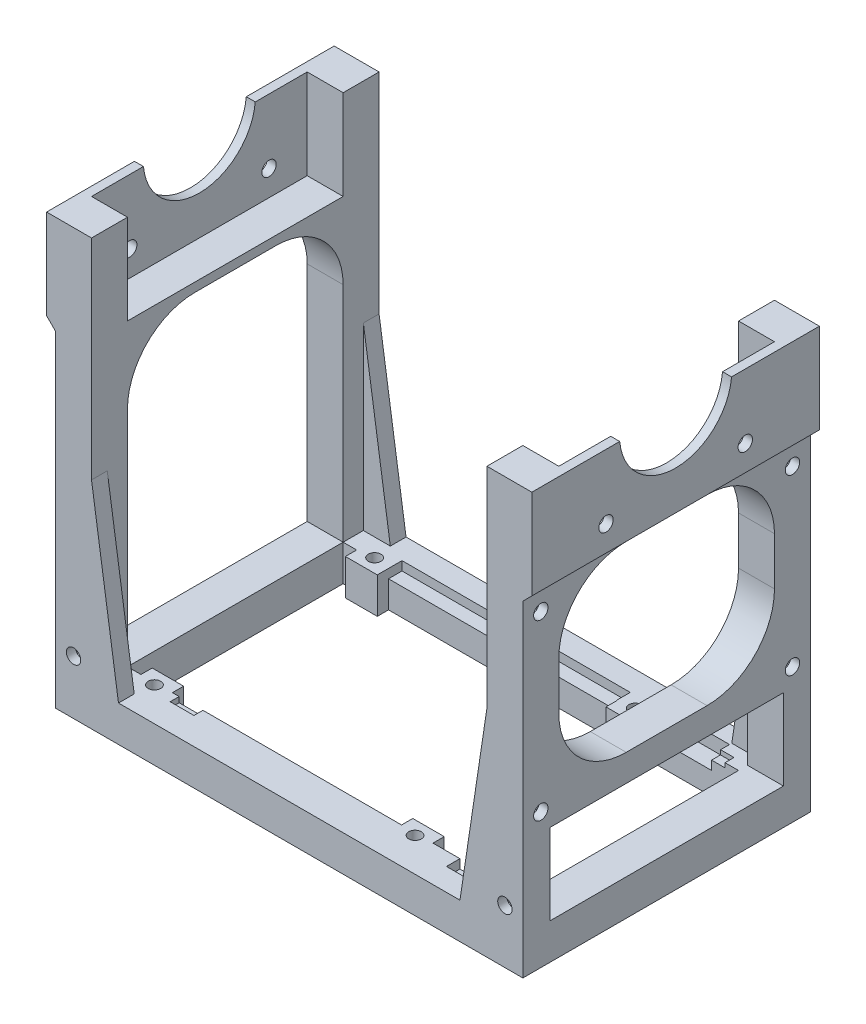
SolidWorks part; units mm, degrees
ref_plane "Płaszczyzna przednia" through (0, 0, 0) normal (0, 0, 1) x (1, 0, 0)
ref_plane "Płaszczyzna górna" through (0, 0, 0) normal (0, 1, 0) x (1, 0, 0)
ref_plane "Płaszczyzna prawa" through (0, 0, 0) normal (1, 0, 0) x (0, 0, -1)
sketch "Szkic1" plane through (0, 0, 0) normal (0, 1, 0) x (1, 0, 0)
  line L1 (0, 0) -> (108, 0)
  line L2 (0, 0) -> (0, 64)
  line L3 (0, 64) -> (108, 64)
  line L4 (108, 0) -> (108, 64)
  line L5 (0, 0) -> (8, 0)
  line L6 (0, 0) -> (0, 8)
  line L7 (0, 8) -> (8, 8)
  line L8 (8, 0) -> (8, 8)
  line L9 (108, 64) -> (100, 64)
  line L10 (108, 64) -> (108, 56)
  line L11 (108, 56) -> (100, 56)
  line L12 (100, 64) -> (100, 56)
  line L13 (8, 8) -> (100, 8)
  line L14 (8, 8) -> (8, 56)
  line L15 (8, 56) -> (100, 56)
  line L16 (100, 8) -> (100, 56)
  line L17 (8, 56) -> (0, 56)
  line L18 (8, 56) -> (8, 64)
  line L19 (8, 64) -> (0, 64)
  line L20 (0, 56) -> (0, 64)
  line L21 (100, 8) -> (108, 8)
  line L22 (100, 8) -> (100, 0)
  line L23 (100, 0) -> (108, 0)
  line L24 (108, 8) -> (108, 0)
extrude "Dodanie-wyciągnięcie1" add sketch "Szkic1" along normal blind 8 contours L14 L17 L2 L7 | L1 L8 L7 L2 | L17 L18 L3 L2 | L18 L15 L12 L3 | L3 L12 L11 L4 | L16 L21 L4 L11 | L21 L22 L1 L4 | L22 L13 L8 L1 region at (4, 0, -4) region at (54, 0, -4) region at (4, 0, -32) region at (104, 0, -4) region at (4, 0, -60) region at (104, 0, -32) region at (54, 0, -60) region at (104, 0, -60)
sketch "Szkic2" plane through (0, 8, 0) normal (0, 1, 0) x (1, 0, 0)
  line L1 (0, 64) -> (8, 64)
  line L2 (0, 64) -> (0, 56)
  line L3 (0, 56) -> (8, 56)
  line L4 (8, 64) -> (8, 56)
  line L5 (8, 8) -> (0, 8)
  line L6 (8, 8) -> (8, 0)
  line L7 (8, 0) -> (0, 0)
  line L8 (0, 8) -> (0, 0)
  line L9 (100, 8) -> (108, 8)
  line L10 (100, 8) -> (100, 0)
  line L11 (100, 0) -> (108, 0)
  line L12 (108, 8) -> (108, 0)
  line L13 (100, 56) -> (108, 56)
  line L14 (100, 56) -> (100, 64)
  line L15 (100, 64) -> (108, 64)
  line L16 (108, 56) -> (108, 64)
extrude "Dodanie-wyciągnięcie3" add sketch "Szkic2" along normal blind 64
sketch "Szkic5" plane through (108, 0, 0) normal (1, 0, 0) x (0, 0, -1)
  line L0 (8, 72) -> (8, 8) construction
  line L1 (6, 8) -> (8, 8)
  line L2 (6, 8) -> (6, 26)
  line L3 (6, 26) -> (8, 26)
  line L4 (8, 8) -> (8, 26)
  line L5 (56, 72) -> (56, 8) construction
  line L6 (58, 8) -> (56, 8)
  line L7 (58, 8) -> (58, 26)
  line L8 (58, 26) -> (56, 26)
  line L9 (56, 8) -> (56, 26)
extrude "Wytnij-wyciągnięcie2" cut sketch "Szkic5" against normal blind 8
sketch "Szkic6" plane through (0, 0, -8) normal (0, 0, -1) x (-1, 0, 0)
  line L0 (-100, 72) -> (-100, 26) construction
  line L1 (-108, 26) -> (-100, 26)
  line L2 (-108, 26) -> (-108, 32)
  line L3 (-108, 32) -> (-100, 32)
  line L4 (-100, 26) -> (-100, 32)
extrude "Dodanie-wyciągnięcie5" add sketch "Szkic6" along normal blind 48
sketch "Szkic7" plane through (0, 8, 0) normal (0, 1, 0) x (1, 0, 0)
  line L0 (8, 56) -> (100, 56) construction
  line L1 (22.1, 56) -> (72.9, 56)
  line L2 (22.1, 56) -> (22.1, 59)
  line L3 (22.1, 59) -> (72.9, 59)
  line L4 (72.9, 56) -> (72.9, 59)
  line L5 (22.1, 54.36) -> (22.1, 56.1) construction
  line L6 (23.37, 57.77) -> (22.1, 57.77) construction
  line L7 (71.63, 57.77) -> (72.9, 57.77) construction
extrude "Wytnij-wyciągnięcie3" cut sketch "Szkic7" against normal blind 2
sketch "Szkic12" plane through (0, 8, 0) normal (0, 1, 0) x (1, 0, 0)
  line L0 (18.5, 57.85) -> (18.5, 55.15) construction
  line L1 (18.5, 56.5) -> (18.5, 53.5) construction
  line L2 (18.5, 56.5) -> (22.1, 56.5)
  line L3 (22.1, 59) -> (22.1, 56) construction
  line L4 (22.1, 56.5) -> (22.1, 53.5)
  line L5 (22.1, 53.5) -> (18.5, 53.5)
  line L6 (18.5, 53.5) -> (15, 53.5)
  line L7 (15, 57) -> (15, 7) construction
  line L8 (15, 53.5) -> (15, 56.5)
  line L9 (15, 56.5) -> (18.5, 56.5)
  circle A0 centre (18.5, 56.5) radius 1.35 construction
  circle A1 centre (18.5, 56.5) radius 1.75
  circle A2 centre (18.5, 56.5) radius 3 construction
  line M23 (8, 56) -> (22.1, 56)
extrude "Dodanie-wyciągnięcie7" add sketch "Szkic12" against normal blind 8 contours A1 L8 L6 L5 L4 M23 | A1 M23 region at (18.5605, 8, -54.5963) region at (18.5, 8, -55.4806)
sketch "Szkic14" plane through (0, 8, 0) normal (0, 1, 0) x (1, 0, 0)
  line L0 (18.5, 8.85) -> (18.5, 6.15) construction
  line L1 (18.5, 7.5) -> (15, 7.5)
  line L2 (15, 57) -> (15, 7) construction
  line L4 (18.5, 10.5) -> (22, 10.5)
  line L5 (22, 10.5) -> (22, 7.5)
  line L6 (22, 7.5) -> (18.5, 7.5)
  line L7 (15, 7.5) -> (15, 10.5)
  line L8 (15, 10.5) -> (18.5, 10.5)
  circle A0 centre (18.5, 7.5) radius 1.35 construction
  circle A1 centre (18.5, 7.5) radius 3 construction
extrude "Dodanie-wyciągnięcie8" add sketch "Szkic14" against normal blind 8
sketch "Szkic15" plane through (0, 8, 0) normal (0, 1, 0) x (1, 0, 0)
  line L0 (76.5, 56.5) -> (76.5, 53.5) construction
  line L1 (76.5, 53.5) -> (73, 53.5)
  line L2 (73, 53.5) -> (73, 56.5)
  line L3 (73, 56.5) -> (76.5, 56.5)
  line L4 (76.5, 56.5) -> (80, 56.5)
  line L5 (80, 56.5) -> (80, 53.5)
  line L6 (80, 53.5) -> (76.5, 53.5)
  circle A0 centre (76.5, 56.5) radius 3 construction
extrude "Dodanie-wyciągnięcie9" add sketch "Szkic15" against normal blind 8
sketch "Szkic16" plane through (0, 8, 0) normal (0, 1, 0) x (1, 0, 0)
  line L0 (76.5, 7.5) -> (76.5, 10.5) construction
  line L1 (76.5, 7.5) -> (80, 7.5)
  line L2 (80, 7.5) -> (80, 10.5)
  line L3 (80, 10.5) -> (76.5, 10.5)
  line L4 (76.5, 10.5) -> (73, 10.5)
  line L5 (73, 10.5) -> (73, 7.5)
  line L6 (73, 7.5) -> (76.5, 7.5)
  circle A0 centre (76.5, 7.5) radius 3 construction
extrude "Dodanie-wyciągnięcie10" add sketch "Szkic16" against normal blind 8
sketch "Szkic17" plane through (0, 8, 0) normal (0, 1, 0) x (1, 0, 0)
  line L0 (18.5, 7.5) -> (21.1, 4.9) construction
  line L1 (73.9, 4.9) -> (79.1, 4.9)
  line L2 (79.1, 4.9) -> (79.1, 10.1)
  line L3 (79.1, 10.1) -> (73.9, 10.1)
  line L4 (73.9, 10.1) -> (73.9, 4.9)
  line L5 (15.9, 59.1) -> (15.9, 53.9)
  line L6 (15.9, 53.9) -> (21.1, 53.9)
  line L7 (21.1, 10.1) -> (15.9, 10.1)
  line L8 (21.1, 10.1) -> (21.1, 4.9)
  line L9 (21.1, 4.9) -> (15.9, 4.9)
  line L10 (15.9, 10.1) -> (15.9, 4.9)
  line L11 (21.1, 53.9) -> (21.1, 59.1)
  line L12 (21.1, 59.1) -> (15.9, 59.1)
  line L13 (79.1, 59.1) -> (73.9, 59.1)
  line L14 (73.9, 59.1) -> (73.9, 53.9)
  line L15 (73.9, 53.9) -> (79.1, 53.9)
  line L16 (79.1, 53.9) -> (79.1, 59.1)
  line L17 (18.5, 7.5) -> (21.1, 10.1) construction
  line L18 (15.9, 4.9) -> (18.5, 7.5) construction
  line L19 (18.5, 7.5) -> (15.9, 10.1) construction
  circle A3 centre (76.5, 7.5) radius 2.6 construction
  circle A4 centre (18.5, 56.5) radius 2.6 construction
  circle A5 centre (76.5, 56.5) radius 2.6 construction
extrude "Wytnij-wyciągnięcie8" cut sketch "Szkic17" against normal blind 4
sketch "Szkic18" plane through (0, 8, 0) normal (0, 1, 0) x (1, 0, 0)
  line L0 (15.9, 53.9) -> (21.1, 59.1) construction
  line L1 (73.9, 53.9) -> (79.1, 59.1) construction
  line L2 (15.9, 10.1) -> (21.1, 4.9) construction
  line L3 (73.9, 10.1) -> (79.1, 4.9) construction
  circle A0 centre (18.5, 56.5) radius 1.4
  circle A1 centre (18.5, 7.5) radius 1.4
  circle A2 centre (76.5, 7.5) radius 1.4
  circle A3 centre (76.5, 56.5) radius 1.4
extrude "Wytnij-wyciągnięcie9" cut sketch "Szkic18" against normal blind 4.5
sketch "Szkic19" plane through (0, 8, 0) normal (0, 1, 0) x (1, 0, 0)
  line L0 (15.9, 53.9) -> (21.1, 59.1) construction
  line L1 (15.9, 53.9) -> (21.1, 53.9)
  line L2 (15.9, 53.9) -> (15.9, 59.1)
  line L3 (15.9, 59.1) -> (21.1, 59.1)
  line L4 (21.1, 53.9) -> (21.1, 59.1)
  line L5 (15.9, 10.1) -> (21.1, 10.1)
  line L6 (15.9, 10.1) -> (15.9, 4.9)
  line L7 (15.9, 4.9) -> (21.1, 4.9)
  line L8 (21.1, 10.1) -> (21.1, 4.9)
  line L9 (73.9, 4.9) -> (79.1, 4.9)
  line L10 (73.9, 4.9) -> (73.9, 10.1)
  line L11 (73.9, 10.1) -> (79.1, 10.1)
  line L12 (79.1, 4.9) -> (79.1, 10.1)
  line L13 (73.9, 53.9) -> (79.1, 53.9)
  line L14 (73.9, 53.9) -> (73.9, 59.1)
  line L15 (73.9, 59.1) -> (79.1, 59.1)
  line L16 (79.1, 53.9) -> (79.1, 59.1)
  line L17 (73.9, 59.1) -> (79.1, 53.9) construction
  line L18 (79.1, 10.1) -> (73.9, 4.9) construction
  line L19 (21.1, 4.9) -> (15.9, 10.1) construction
  circle A0 centre (18.5, 56.5) radius 1.4
  circle A1 centre (76.5, 56.5) radius 1.4
  circle A2 centre (18.5, 7.5) radius 1.4
  circle A3 centre (76.5, 7.5) radius 1.4
extrude "Dodanie-wyciągnięcie11" add sketch "Szkic19" against normal blind 2.3
sketch "Szkic21" plane through (8, 0, 0) normal (1, 0, 0) x (0, 0, -1)
  line L1 (56, 8) -> (8, 8)
  line L2 (56, 8) -> (56, 0)
  line L3 (56, 0) -> (8, 0)
  line L4 (8, 8) -> (8, 0)
  line L5 (56, 8) -> (64, 8)
  line L6 (56, 8) -> (56, 72)
  line L7 (56, 72) -> (64, 72)
  line L8 (64, 8) -> (64, 72)
  line L9 (0, 72) -> (8, 72)
  line L10 (0, 72) -> (0, 8)
  line L11 (0, 8) -> (8, 8)
  line L12 (8, 72) -> (8, 8)
  line M9 (56, 8) -> (64, 8)
  line M10 (64, 8) -> (64, 72)
  line M11 (64, 72) -> (56, 72)
  line M12 (56, 72) -> (56, 8)
extrude "Dodanie-wyciągnięcie12" add sketch "Szkic21" along normal blind 4 contours M12 M9 M10 M11 | L12 L9 L10 L11 | L2 L1 L4 L3 region at (8, 40, -4) region at (8, 40, -60)
sketch "Szkic22" plane through (0, 0, 0) normal (0, -1, 0) x (1, 0, 0)
  line L0 (0, -64) -> (108, -64) construction
  line L1 (0, 0) -> (4, 0)
  line L2 (0, 0) -> (0, -64)
  line L3 (0, -64) -> (4, -64)
  line L4 (4, 0) -> (4, -64)
extrude "Wytnij-wyciągnięcie11" cut sketch "Szkic22" against normal blind 84 contours L2 L1 L4 L3
ref_plane "Płaszczyzna1" through (12, 8, -56) normal (1, 0, 0) x (0, 0, -1)
sketch "Szkic24" plane through (0, 72, 0) normal (0, 1, 0) x (1, 0, 0)
  line L1 (4, 64) -> (12, 64)
  line L2 (4, 64) -> (4, 56)
  line L3 (4, 56) -> (12, 56)
  line L4 (12, 64) -> (12, 56)
  line L5 (4, 8) -> (12, 8)
  line L6 (4, 8) -> (4, 0)
  line L7 (4, 0) -> (12, 0)
  line L8 (12, 8) -> (12, 0)
  line L9 (100, 8) -> (108, 8)
  line L10 (100, 8) -> (100, 0)
  line L11 (100, 0) -> (108, 0)
  line L12 (108, 8) -> (108, 0)
  line L13 (100, 64) -> (108, 64)
  line L14 (100, 64) -> (100, 56)
  line L15 (100, 56) -> (108, 56)
  line L16 (108, 64) -> (108, 56)
extrude "Dodanie-wyciągnięcie13" add sketch "Szkic24" along normal blind 2.64 contours L8 L5 L6 L7 | L12 L9 L10 L11 | L16 L13 L14 L15 | L2 L1 L4 L3 region at (8, 72, -4) region at (104, 72, -4) region at (104, 72, -60)
sketch "Szkic25" plane through (0, 0, -8) normal (0, 0, -1) x (-1, 0, 0)
  line L0 (-100, 74.64) -> (-100, 32) construction
  line L1 (-108, 74.64) -> (-100, 74.64)
  line L2 (-108, 74.64) -> (-108, 72.64)
  line L3 (-108, 72.64) -> (-100, 72.64)
  line L4 (-100, 74.64) -> (-100, 72.64)
  line L5 (-4, 74.64) -> (-4, 8) construction
  line L6 (-12, 74.64) -> (-4, 74.64)
  line L7 (-12, 74.64) -> (-12, 72.64)
  line L8 (-12, 72.64) -> (-4, 72.64)
  line L9 (-4, 74.64) -> (-4, 72.64)
extrude "Dodanie-wyciągnięcie14" add sketch "Szkic25" along normal blind 48
sketch "Szkic26" plane through (0, 74.64, 0) normal (0, 1, 0) x (1, 0, 0)
  line L1 (4, 64) -> (12, 64)
  line L2 (4, 64) -> (4, 56)
  line L3 (4, 56) -> (12, 56)
  line L4 (12, 64) -> (12, 56)
  line L5 (4, 0) -> (12, 0)
  line L6 (4, 0) -> (4, 8)
  line L7 (4, 8) -> (12, 8)
  line L8 (12, 0) -> (12, 8)
  line L9 (108, 0) -> (100, 0)
  line L10 (108, 0) -> (108, 8)
  line L11 (108, 8) -> (100, 8)
  line L12 (100, 0) -> (100, 8)
  line L13 (108, 64) -> (100, 64)
  line L14 (108, 64) -> (108, 56)
  line L15 (108, 56) -> (100, 56)
  line L16 (100, 64) -> (100, 56)
extrude "Dodanie-wyciągnięcie15" add sketch "Szkic26" along normal blind 20
sketch "Szkic27" plane through (4, 0, 0) normal (-1, 0, 0) x (0, 0, 1)
  line L0 (-56, 72.64) -> (-64, 72.64) construction
  line L1 (-64, 94.64) -> (-64, 0) construction
  line L3 (-64, 72.64) -> (0, 72.64)
  line L4 (-64, 72.64) -> (-64, 94.64)
  line L5 (-64, 94.64) -> (0, 94.64)
  line L6 (0, 72.64) -> (0, 94.64)
  circle A0 centre (-32, 95.79) radius 11
  circle A1 centre (-32, 95.79) radius 12.5
  circle A2 centre (-47.5, 80.29) radius 1.6
  circle A3 centre (-16.5, 80.29) radius 1.6
  line M6 (-8, 74.64) -> (-56, 74.64)
  line M7 (-56, 74.64) -> (-56, 94.64)
  line M8 (-56, 94.64) -> (-64, 94.64)
  line M9 (-64, 94.64) -> (-64, 0)
  line M11 (0, 0) -> (0, 94.64)
  line M12 (0, 94.64) -> (-8, 94.64)
  line M13 (-8, 94.64) -> (-8, 74.64)
  line M15 (-56, 72.64) -> (-8, 72.64)
extrude "Dodanie-wyciągnięcie16" add sketch "Szkic27" along normal blind 2 contours A1 L5 M7 M6 M13 | L3 M9 M15 M11 M12 M13 M6 M7 M8 region at (4, 83.64, -63.3232) region at (4, 83.181, -32)
sketch "Szkic28" plane through (108, 0, 0) normal (1, 0, 0) x (0, 0, -1)
  line L1 (64, 94.64) -> (0, 94.64)
  line L2 (64, 94.64) -> (64, 72.64)
  line L3 (64, 72.64) -> (0, 72.64)
  line L4 (0, 94.64) -> (0, 72.64)
  circle A0 centre (32, 95.79) radius 12.5
  circle A1 centre (16.5, 80.29) radius 1.6
  circle A2 centre (47.5, 80.29) radius 1.6
  line M2 (8, 72.64) -> (56, 72.64)
  line M10 (64, 0) -> (64, 94.64)
  line M11 (64, 94.64) -> (56, 94.64)
  line M12 (56, 94.64) -> (56, 74.64)
  line M13 (56, 74.64) -> (8, 74.64)
  line M14 (8, 74.64) -> (8, 94.64)
  line M15 (8, 94.64) -> (0, 94.64)
  line M16 (0, 94.64) -> (0, 0)
extrude "Dodanie-wyciągnięcie17" add sketch "Szkic28" along normal blind 2 contours L3 M10 M11 M12 M13 M14 M15 M16 M2 | A0 L1 M14 M13 M12 region at (108, 83.64, -63.3232) region at (108, 83.181, -32)
chamfer "Sfazowanie1" distance 2 angle 45 2 edges at (2, 72.64, -32) (110, 72.64, -32)
sketch "Szkic29" plane through (0, 0, 0) normal (0, 0, 1) x (1, 0, 0)
  line L0 (12, 8) -> (4, 8.1) construction
  line L1 (4, 72.64) -> (4, 0) construction
  line L2 (4, 8.1) -> (4, 16.1) construction
  line L3 (4, 16.1) -> (12, 8) construction
  line L4 (100, 8) -> (108, 8) construction
  line L5 (5.1892, 14.8959) -> (5.1541, 9.2392)
  line L6 (5.1541, 9.2392) -> (10.8108, 9.2041)
  line L7 (10.8108, 9.2041) -> (10.8459, 14.8608)
  line L8 (10.8459, 14.8608) -> (5.1892, 14.8959)
  line L9 (108, 72.64) -> (108, 0) construction
  line L10 (108, 8) -> (108, 16) construction
  line L11 (108, 16) -> (100, 8) construction
  line L13 (106.8284, 14.8284) -> (101.1716, 14.8284)
  line L14 (101.1716, 14.8284) -> (101.1716, 9.1716)
  line L15 (101.1716, 9.1716) -> (106.8284, 9.1716)
  line L16 (106.8284, 9.1716) -> (106.8284, 14.8284)
  circle A0 centre (8, 12.05) radius 4 construction
  circle A1 centre (104, 12) radius 4 construction
  circle A2 centre (8, 12.05) radius 1.6
  circle A3 centre (104, 12) radius 1.6
extrude "Wytnij-wyciągnięcie12" cut sketch "Szkic29" against normal blind 4 contours L5 L6 L7 L8 | L13 L14 L15 L16
extrude "Wytnij-wyciągnięcie13" cut sketch "Szkic29<4>" against normal blind 4.2 contours A3 | A2
sketch "Szkic29<4>" plane through (0, 0, 0) normal (0, 0, 1) x (1, 0, 0) same geometry as "Szkic29"
extrude "Dodanie-wyciągnięcie18" add sketch "Szkic29<7>" against normal blind 2 contours L6 L7 L8 L5 | A2 | L15 L16 L13 L14 | A3
sketch "Szkic29<7>" plane through (0, 0, 0) normal (0, 0, 1) x (1, 0, 0) same geometry as "Szkic29"
sketch "Szkic30" plane through (0, 0, -64) normal (0, 0, -1) x (-1, 0, 0)
  line L0 (-100, 8) -> (-108, 8) construction
  line L1 (-108, 8) -> (-108, 16) construction
  line L2 (-108, 72.64) -> (-108, 0) construction
  line L3 (-108, 16) -> (-100, 8) construction
  line L4 (-12, 8) -> (-4, 8) construction
  line L5 (-4, 72.64) -> (-4, 0) construction
  line L6 (-4, 8) -> (-4, 16) construction
  line L7 (-4, 16) -> (-12, 8) construction
  line L9 (-5.1716, 14.8284) -> (-10.8284, 14.8284)
  line L10 (-10.8284, 14.8284) -> (-10.8284, 9.1716)
  line L11 (-10.8284, 9.1716) -> (-5.1716, 9.1716)
  line L12 (-5.1716, 9.1716) -> (-5.1716, 14.8284)
  line L13 (-106.8284, 14.8284) -> (-106.8284, 9.1716)
  line L14 (-106.8284, 9.1716) -> (-101.1716, 9.1716)
  line L15 (-101.1716, 9.1716) -> (-101.1716, 14.8284)
  line L16 (-101.1716, 14.8284) -> (-106.8284, 14.8284)
  circle A0 centre (-8, 12) radius 4 construction
  circle A1 centre (-104, 12) radius 4 construction
  circle A2 centre (-104, 12) radius 1.6
  circle A3 centre (-8, 12) radius 1.6
extrude "Wytnij-wyciągnięcie14" cut sketch "Szkic30" against normal blind 4 contours L15 L16 L13 L14 A2 | A3 | L11 L12 L9 L10 A3 | A2 region at (5.2516, 12, -64) region at (104, 14.7484, -64) region at (8, 12, -64)
extrude "Wytnij-wyciągnięcie15" cut sketch "Szkic30<6>" against normal blind 4.2 contours A2 | A3
sketch "Szkic30<6>" plane through (0, 0, -64) normal (0, 0, -1) x (-1, 0, 0) same geometry as "Szkic30"
extrude "Dodanie-wyciągnięcie20" add sketch "Szkic30<8>" against normal blind 2 contours A3 | L11 L12 L9 L10 | A2 | L14 L15 L16 L13
sketch "Szkic30<8>" plane through (0, 0, -64) normal (0, 0, -1) x (-1, 0, 0) same geometry as "Szkic30"
sketch "Szkic31" plane through (4, 0, 0) normal (-1, 0, 0) x (0, 0, 1)
  line L0 (-64, 72.64) -> (-64, 64.64) construction
  line L1 (-64, 72.64) -> (-64, 0) construction
  line L2 (-64, 0) -> (-64, 16) construction
  line L3 (-64, 16) -> (-64, 24) construction
  line L4 (0, 0) -> (0, 16) construction
  line L5 (0, 72.64) -> (0, 0) construction
  line L6 (0, 16) -> (0, 24) construction
  line L7 (0, 72.64) -> (0, 64.64) construction
  line L8 (0, 64.64) -> (-8, 64.64) construction
  line L9 (-8, 72.64) -> (-8, 8) construction
  line L10 (-8, 64.64) -> (0, 72.64) construction
  line L11 (-64, 64.64) -> (-56, 64.64) construction
  line L12 (-56, 8) -> (-56, 72.64) construction
  line L13 (-56, 64.64) -> (-64, 72.64) construction
  line L14 (-64, 24) -> (-56, 24) construction
  line L15 (-56, 24) -> (-64, 16) construction
  line L16 (0, 24) -> (-8, 24) construction
  line L17 (-8, 24) -> (0, 16) construction
  line L19 (-57.1716, 22.8284) -> (-62.8284, 22.8284)
  line L20 (-62.8284, 22.8284) -> (-62.8284, 17.1716)
  line L21 (-62.8284, 17.1716) -> (-57.1716, 17.1716)
  line L22 (-57.1716, 17.1716) -> (-57.1716, 22.8284)
  line L23 (-6.8284, 22.8284) -> (-6.8284, 17.1716)
  line L24 (-6.8284, 17.1716) -> (-1.1716, 17.1716)
  line L25 (-1.1716, 17.1716) -> (-1.1716, 22.8284)
  line L26 (-1.1716, 22.8284) -> (-6.8284, 22.8284)
  line L27 (-6.8284, 65.8116) -> (-1.1716, 65.8116)
  line L28 (-1.1716, 65.8116) -> (-1.1716, 71.4684)
  line L29 (-1.1716, 71.4684) -> (-6.8284, 71.4684)
  line L30 (-6.8284, 71.4684) -> (-6.8284, 65.8116)
  line L31 (-57.1716, 65.8116) -> (-57.1716, 71.4684)
  line L32 (-57.1716, 71.4684) -> (-62.8284, 71.4684)
  line L33 (-62.8284, 71.4684) -> (-62.8284, 65.8116)
  line L34 (-62.8284, 65.8116) -> (-57.1716, 65.8116)
  circle A0 centre (-60, 20) radius 4 construction
  circle A1 centre (-4, 20) radius 4 construction
  circle A2 centre (-4, 68.64) radius 4 construction
  circle A3 centre (-60, 68.64) radius 4 construction
  circle A4 centre (-60, 20) radius 1.6
  circle A5 centre (-4, 20) radius 1.6
  circle A6 centre (-4, 68.64) radius 1.6
  circle A7 centre (-60, 68.64) radius 1.6
extrude "Wytnij-wyciągnięcie16" cut sketch "Szkic31" against normal blind 4
extrude "Wytnij-wyciągnięcie17" cut sketch "Szkic31<2>" against normal blind 4.2 contours A4 | A5 | A6 | A7
sketch "Szkic31<2>" plane through (4, 0, 0) normal (-1, 0, 0) x (0, 0, 1) same geometry as "Szkic31"
extrude "Dodanie-wyciągnięcie21" add sketch "Szkic31<3>" against normal blind 2 contours L21 L22 L19 L20 | L24 L25 L26 L23 | L27 L28 L29 L30 | A4 | A5 | A6 | A7 | L34 L31 L32 L33
sketch "Szkic31<3>" plane through (4, 0, 0) normal (-1, 0, 0) x (0, 0, 1) same geometry as "Szkic31"
sketch "Szkic32" plane through (108, 0, 0) normal (1, 0, 0) x (0, 0, -1)
  line L0 (0, 72.64) -> (0, 64.64) construction
  line L1 (0, 72.64) -> (0, 0) construction
  line L2 (0, 64.64) -> (8, 64.64) construction
  line L3 (8, 72.64) -> (8, 32) construction
  line L4 (8, 64.64) -> (0, 72.64) construction
  line L5 (64, 72.64) -> (64, 64.64) construction
  line L6 (64, 72.64) -> (64, 0) construction
  line L7 (64, 64.64) -> (56, 64.64) construction
  line L8 (56, 72.64) -> (56, 32) construction
  line L9 (56, 64.64) -> (64, 72.64) construction
  line L10 (0, 0) -> (0, 26) construction
  line L12 (64, 0) -> (64, 26) construction
  line L13 (64, 26) -> (56, 26) construction
  line L14 (58, 26) -> (6, 26) construction
  line L15 (0, 26) -> (0, 34) construction
  line L16 (0, 26) -> (8, 26) construction
  line L17 (8, 26) -> (0, 34) construction
  line L18 (64, 26) -> (64, 34) construction
  line L19 (64, 34) -> (56, 26) construction
  line L20 (57.1716, 65.8116) -> (62.8284, 65.8116)
  line L21 (6.8284, 65.8116) -> (6.8284, 71.4684)
  line L22 (6.8284, 71.4684) -> (1.1716, 71.4684)
  line L23 (1.1716, 71.4684) -> (1.1716, 65.8116)
  line L24 (1.1716, 65.8116) -> (6.8284, 65.8116)
  line L25 (62.8284, 65.8116) -> (62.8284, 71.4684)
  line L26 (62.8284, 71.4684) -> (57.1716, 71.4684)
  line L27 (57.1716, 71.4684) -> (57.1716, 65.8116)
  line L28 (57.1716, 27.1716) -> (62.8284, 27.1716)
  line L29 (62.8284, 27.1716) -> (62.8284, 32.8284)
  line L30 (62.8284, 32.8284) -> (57.1716, 32.8284)
  line L31 (57.1716, 32.8284) -> (57.1716, 27.1716)
  line L32 (6.8284, 27.1716) -> (6.8284, 32.8284)
  line L33 (6.8284, 32.8284) -> (1.1716, 32.8284)
  line L34 (1.1716, 32.8284) -> (1.1716, 27.1716)
  line L35 (1.1716, 27.1716) -> (6.8284, 27.1716)
  circle A0 centre (4, 68.64) radius 4 construction
  circle A1 centre (60, 68.64) radius 4 construction
  circle A2 centre (60, 30) radius 4 construction
  circle A3 centre (4, 30) radius 4 construction
  circle A4 centre (4, 68.64) radius 1.6
  circle A5 centre (60, 68.64) radius 1.6
  circle A6 centre (60, 30) radius 1.6
  circle A7 centre (4, 30) radius 1.6
extrude "Wytnij-wyciągnięcie18" cut sketch "Szkic32" against normal blind 4
extrude "Wytnij-wyciągnięcie19" cut sketch "Szkic32<2>" against normal blind 4.2 contours A4 | A5 | A6 | A7
sketch "Szkic32<2>" plane through (108, 0, 0) normal (1, 0, 0) x (0, 0, -1) same geometry as "Szkic32"
extrude "Dodanie-wyciągnięcie22" add sketch "Szkic32<3>" against normal blind 2 contours L20 L25 L26 L27 | L28 L29 L30 L31 | A4 | L24 L21 L22 L23 | A5 | A6 | A7 | L35 L32 L33 L34
sketch "Szkic32<3>" plane through (108, 0, 0) normal (1, 0, 0) x (0, 0, -1) same geometry as "Szkic32"
sketch "Szkic33" plane through (0, 0, 0) normal (0, -1, 0) x (1, 0, 0)
  line L0 (12, -56) -> (12, -64) construction
  line L1 (4, -64) -> (108, -64) construction
  line L2 (12, -64) -> (4, -64) construction
  line L3 (4, 0) -> (4, -64) construction
  line L4 (4, -64) -> (12, -56) construction
  line L5 (12, -8) -> (4, -8) construction
  line L6 (4, -8) -> (4, 0) construction
  line L7 (4, 0) -> (108, 0) construction
  line L8 (4, 0) -> (12, -8) construction
  line L9 (100, -8) -> (108, -8) construction
  line L10 (108, 0) -> (108, -64) construction
  line L11 (108, -8) -> (108, 0) construction
  line L12 (108, 0) -> (100, -8) construction
  line L13 (100, -56) -> (108, -56) construction
  line L14 (108, -56) -> (108, -64) construction
  line L15 (108, -64) -> (100, -56) construction
  line L17 (10.8284, -57.1716) -> (5.1716, -57.1716)
  line L18 (5.1716, -57.1716) -> (5.1716, -62.8284)
  line L19 (5.1716, -62.8284) -> (10.8284, -62.8284)
  line L20 (10.8284, -62.8284) -> (10.8284, -57.1716)
  line L21 (101.1716, -57.1716) -> (101.1716, -62.8284)
  line L22 (101.1716, -62.8284) -> (106.8284, -62.8284)
  line L23 (106.8284, -62.8284) -> (106.8284, -57.1716)
  line L24 (106.8284, -57.1716) -> (101.1716, -57.1716)
  line L25 (101.1716, -6.8284) -> (106.8284, -6.8284)
  line L26 (106.8284, -6.8284) -> (106.8284, -1.1716)
  line L27 (106.8284, -1.1716) -> (101.1716, -1.1716)
  line L28 (101.1716, -1.1716) -> (101.1716, -6.8284)
  line L29 (10.8284, -6.8284) -> (10.8284, -1.1716)
  line L30 (10.8284, -1.1716) -> (5.1716, -1.1716)
  line L31 (5.1716, -1.1716) -> (5.1716, -6.8284)
  line L32 (5.1716, -6.8284) -> (10.8284, -6.8284)
  circle A0 centre (8, -60) radius 4 construction
  circle A1 centre (104, -60) radius 4 construction
  circle A2 centre (104, -4) radius 4 construction
  circle A3 centre (8, -4) radius 4 construction
  circle A4 centre (8, -4) radius 1.6
  circle A5 centre (104, -4) radius 1.6
  circle A6 centre (104, -60) radius 1.6
  circle A7 centre (8, -60) radius 1.6
extrude "Wytnij-wyciągnięcie20" cut sketch "Szkic33" against normal blind 4
extrude "Wytnij-wyciągnięcie21" cut sketch "Szkic33<2>" against normal blind 4.2 contours A4 | A5 | A6 | A7
sketch "Szkic33<2>" plane through (0, 0, 0) normal (0, -1, 0) x (1, 0, 0) same geometry as "Szkic33"
extrude "Dodanie-wyciągnięcie23" add sketch "Szkic33<3>" against normal blind 2 contours L19 L20 L17 L18 | L25 L26 L27 L28 | L22 L23 L24 L21 | A4 | A5 | A6 | A7 | L32 L29 L30 L31
sketch "Szkic33<3>" plane through (0, 0, 0) normal (0, -1, 0) x (1, 0, 0) same geometry as "Szkic33"
sketch "Szkic36" plane through (0, 0, 0) normal (0, 0, 1) x (1, 0, 0)
  line L0 (12, 8) -> (18, 8)
  line L1 (12, 8) -> (12, 48)
  line L2 (12, 94.64) -> (12, 8) construction
  line L4 (100, 8) -> (94, 8)
  line L5 (12, 8) -> (100, 8) construction
  line L6 (100, 8) -> (100, 48)
  line L7 (100, 94.64) -> (100, 8) construction
  line L8 (18, 8) -> (12, 48)
  line L9 (94, 8) -> (100, 48)
extrude "Dodanie-wyciągnięcie24" add sketch "Szkic36" against normal blind 3.5
sketch "Szkic37" plane through (0, 0, -64) normal (0, 0, -1) x (-1, 0, 0)
  line L0 (-12, 8) -> (-18, 8)
  line L1 (-12, 8) -> (-100, 8) construction
  line L2 (-12, 8) -> (-12, 48)
  line L3 (-100, 8) -> (-94, 8)
  line L4 (-100, 8) -> (-100, 48)
  line L5 (-100, 94.64) -> (-100, 8) construction
  line L6 (-94, 8) -> (-100, 48)
  line L7 (-18, 8) -> (-12, 48)
extrude "Dodanie-wyciągnięcie25" add sketch "Szkic37" against normal blind 3.5
fillet "Zaokrąglenie1" radius 15 6 edges at (8, 72.64, -8) (104, 72.64, -8) (8, 72.64, -56) (104, 72.64, -56) (104, 32, -56) (104, 32, -8)
chamfer "Sfazowanie2" distance 4 distance2 1 1 edges at (100, 26, -32) first distance on face at (104, 26, -32)
sketch "Szkic38" plane through (0, 0, -8) normal (0, 0, -1) x (-1, 0, 0)
  line L0 (-22, 8) -> (-23.5, 8) construction
  line L1 (-22, 8) -> (-22, 0) construction
  line L2 (-22, 8) -> (-73, 8) construction
  line L3 (-23.5, 8) -> (-28.8, 8)
  line L4 (-23.5, 8) -> (-23.5, 6.8)
  line L5 (-23.5, 6.8) -> (-28.8, 6.8)
  line L6 (-28.8, 6.8) -> (-28.8, 8)
extrude "Wytnij-wyciągnięcie22" cut sketch "Szkic38" against normal blind 2
sketch "Szkic39" plane through (0, 0, -56) normal (0, 0, 1) x (1, 0, 0)
  line L0 (80, 8) -> (85, 8)
  line L1 (80, 8) -> (80, 0) construction
  line L2 (80, 8) -> (100, 8) construction
  line L3 (80, 8) -> (80, 6)
  line L4 (80, 6) -> (85, 6)
  line L5 (85, 6) -> (85, 8)
extrude "Wytnij-wyciągnięcie23" cut sketch "Szkic39" against normal blind 3
sketch "Szkic40" plane through (0, 0, -56) normal (0, 0, 1) x (1, 0, 0)
  line L0 (85, 8) -> (94, 8)
  line L1 (85, 6) -> (85, 8) construction
  line L2 (85, 8) -> (100, 8) construction
  line L3 (85, 8) -> (85, 5)
  line L4 (85, 5) -> (94, 5)
  line L5 (94, 5) -> (94, 8)
extrude "Wytnij-wyciągnięcie24" cut sketch "Szkic40" against normal blind 4 contours L5 L0 L3 L4
sketch "Szkic41" plane through (0, 0, -56) normal (0, 0, 1) x (1, 0, 0)
  line L0 (94, 5) -> (94, 8) construction
  line L1 (94, 8) -> (97, 8)
  line L2 (94, 8) -> (94, 7)
  line L3 (94, 7) -> (97, 7)
  line L4 (97, 8) -> (97, 7)
  line L5 (94, 8) -> (100, 8) construction
extrude "Wytnij-wyciągnięcie25" cut sketch "Szkic41" against normal blind 2
sketch "Szkic42" plane through (0, 0, -8) normal (0, 0, -1) x (-1, 0, 0)
  line L0 (-80, 8) -> (-85.9976, 8) construction
  line L1 (-80, 8) -> (-80, 0) construction
  line L2 (-80, 8) -> (-100, 8) construction
  line L4 (-85.9976, 8) -> (-93.9976, 8)
  line L5 (-85.9976, 8) -> (-85.9976, 6)
  line L6 (-85.9976, 6) -> (-93.9976, 6)
  line L7 (-93.9976, 8) -> (-93.9976, 6)
  point P9 (0, 0)
extrude "Wytnij-wyciągnięcie26" cut sketch "Szkic42" against normal blind 3
